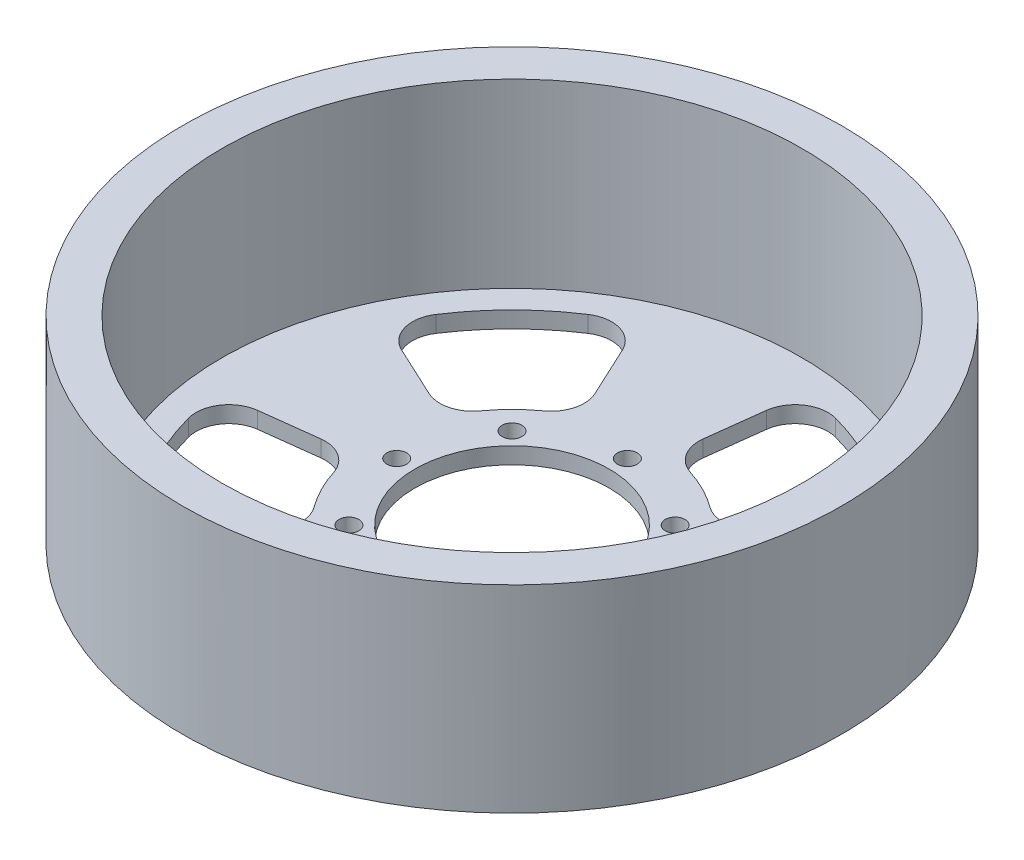
SolidWorks part; units mm, degrees
material "7050-T73510"
ref_plane "前视基准面" through (0, 0, 0) normal (0, 0, 1) x (1, 0, 0)
ref_plane "上视基准面" through (0, 0, 0) normal (0, 1, 0) x (1, 0, 0)
ref_plane "右视基准面" through (0, 0, 0) normal (1, 0, 0) x (0, 0, -1)
sketch "草图1" plane through (0, 0, 0) normal (0, 1, 0) x (1, 0, 0)
  circle A0 centre (0, 0) radius 50
  dimension "D1" = 100
extrude "凸台-拉伸1" add sketch "草图1" along normal blind 50
sketch "草图2" plane through (0, 50, 0) normal (0, 1, 0) x (1, 0, 0)
  circle A0 centre (0, 0) radius 44
  dimension "D1" = 88
extrude "切除-拉伸1" cut sketch "草图2" against normal blind 37.5
sketch "草图3" plane through (0, 0, 0) normal (0, -1, 0) x (1, 0, 0)
  circle A0 centre (0, 0) radius 44
  dimension "D1" = 88
extrude "切除-拉伸2" cut sketch "草图3" against normal blind 9.5
sketch "草图4" plane through (0, 12.5, 0) normal (0, 1, 0) x (1, 0, 0)
  circle A0 centre (0, 0) radius 14.75
  circle A1 centre (0, 0) radius 17.5 construction
  circle A2 centre (0, 17.5) radius 1.5
  circle A3 centre (12.3744, 12.3744) radius 1.5
  circle A4 centre (17.5, 0) radius 1.5
  circle A5 centre (12.3744, -12.3744) radius 1.5
  circle A6 centre (0, -17.5) radius 1.5
  circle A7 centre (-12.3744, -12.3744) radius 1.5
  circle A8 centre (-17.5, 0) radius 1.5
  circle A9 centre (-12.3744, 12.3744) radius 1.5
  point P22 (0, 0)
  dimension "D1" = 29.5
  dimension "D2" = 35
  dimension "D3" = 3
extrude "切除-拉伸3" cut sketch "草图4" against normal blind 4
sketch "草图5" plane through (0, 50, 0) normal (0, 1, 0) x (1, 0, 0)
  circle A0 centre (0, 0) radius 46.5
  dimension "D1" = 93
split line "分割线1"
sketch "草图7" plane through (0, 50, 0) normal (0, 1, 0) x (1, 0, 0)
  circle A0 centre (0, 0) radius 46.5
  dimension "D1" = 93
split line "分割线2"
sketch "草图8" plane through (0, 12.5, 0) normal (0, 1, 0) x (1, 0, 0)
  line L0 (0, 0) -> (18.1596, 35.6403) construction
  line L2 (0, 0) -> (0, 67.2498) construction
  line L10 (0, 0) -> (4.8748, 39.7018)
  line L11 (0, 0) -> (29.2541, 27.2799)
  circle A8 centre (0, 0) radius 21.5
  circle A9 centre (0, 0) radius 40
  dimension "D1" = 43
  dimension "D2" = 80
  dimension "D3" = 27
  dimension "D4" = 20
extrude "切除-拉伸4" cut sketch "草图8" against normal blind 4 contours L11 A9 L10 A8 region at (14.091, 12.5, -27.6552)
fillet "圆角1" radius 5 4 edges at (29.2541, 11, -27.2799) (15.7241, 11, -14.663) (2.6202, 11, -21.3397) (4.8748, 11, -39.7018)
pattern_circular "阵列(圆周)1" count 5 over 360 about axis through (0, 50, 0) along (0, 1, 0) of "切除-拉伸4", "圆角1"
sketch "草图9" plane through (0, 0, 0) normal (0, -1, 0) x (1, 0, 0)
  circle A0 centre (0, 0) radius 46.5
  circle A1 centre (0, 0) radius 72.0126
  dimension "D1" = 93
sketch "草图11" plane through (0, 0, 0) normal (0, -1, 0) x (1, 0, 0)
  circle A0 centre (0, 0) radius 59.1651
extrude "切除-拉伸8" cut sketch "草图11" against normal blind 10
sketch "草图12" plane through (0, 10, 0) normal (0, -1, 0) x (1, 0, 0)
  circle A0 centre (0, 0) radius 46.5
  dimension "D1" = 93
split line "分割线3"
sketch "草图15" plane through (0, 50, 0) normal (0, 1, 0) x (1, 0, 0)
  circle A0 centre (0, 0) radius 58.0487
extrude "切除-拉伸10" cut sketch "草图15" against normal blind 10
sketch "草图16" plane through (0, 40, 0) normal (0, 1, 0) x (1, 0, 0)
  circle A0 centre (0, 0) radius 47
  circle A1 centre (0, 0) radius 50 construction
  circle A2 centre (0, 0) radius 50
  dimension "D1" = 94
extrude "切除-拉伸11" [suppressed] cut sketch "草图16" against normal blind 77
